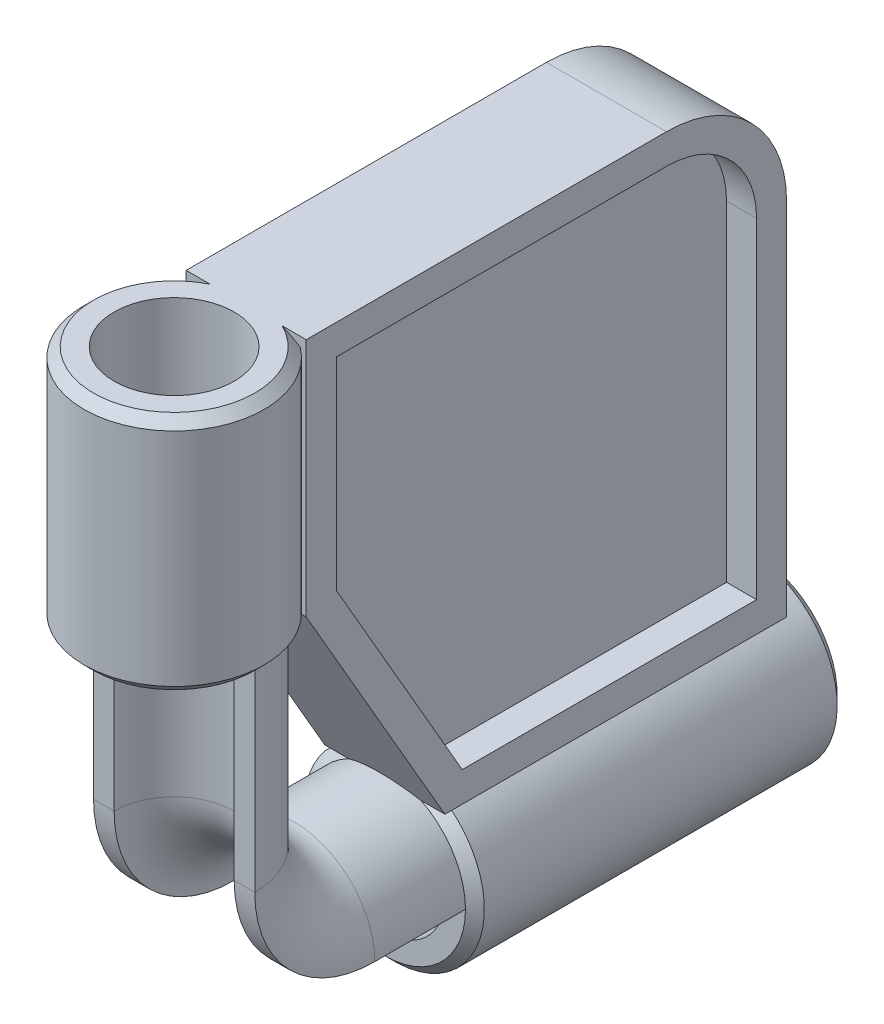
SolidWorks part; units mm, degrees
ref_plane "Front Plane" through (0, 0, 0) normal (1, 0, 0) x (0, 1, 0)
ref_plane "Top Plane" through (0, 0, 0) normal (0, 0, 1) x (0, 1, 0)
ref_plane "Right Plane" through (0, 0, 0) normal (0, 1, 0) x (-1, 0, 0)
sketch "Sketch1" plane through (0, 0, 0) normal (1, 0, 0) x (0, 1, 0)
  line L0 (-25.4, 10.7353) -> (0, 25.4)
  line L1 (-25.4, -25.4) -> (25.4, -25.4)
  line L2 (-25.4, -25.4) -> (-25.4, 10.7353)
  line L3 (0, 25.4) -> (25.4, 25.4)
  line L4 (25.4, -25.4) -> (25.4, 25.4)
  line L5 (0, -55) -> (0, 55) construction
  line L6 (55, 0) -> (-55, 0) construction
  point P0 (0, 0)
  point P10 (25.4, 0)
  dimension "D1" = 50.8
  dimension "D2" = 50.8
  dimension "D3" = 30
  dimension "D4" = 25.4
extrude "Boss-Extrude1" add sketch "Sketch1" along normal mid plane 12.7
fillet "Fillet1" radius 12.7 1 edges at (0, 25.4, -25.4)
sketch "Sketch3" plane through (6.35, 0, 0) normal (1, 0, 0) x (0, 1, 0)
  line L10 (-22.225, -22.225) -> (12.7, -22.225)
  line L11 (22.225, -12.7) -> (22.225, 22.225)
  line L12 (22.225, 22.225) -> (0.8507, 22.225)
  line L13 (0.8507, 22.225) -> (-22.225, 8.9022)
  line L14 (-22.225, 8.9022) -> (-22.225, -22.225)
  line L15 (-22.225, -22.225) -> (12.7, -22.225)
  line L16 (22.225, -12.7) -> (22.225, 22.225)
  line L17 (22.225, 22.225) -> (0.8507, 22.225)
  line L18 (0.8507, 22.225) -> (-22.225, 8.9022)
  line L19 (-22.225, 8.9022) -> (-22.225, -22.225)
  arc A2 (12.7, -22.225) -> (22.225, -12.7) centre (12.7, -12.7) ccw
  arc A3 (12.7, -22.225) -> (22.225, -12.7) centre (12.7, -12.7) ccw
  dimension "D1" = 3.175
extrude "Cut-Extrude2" cut sketch "Sketch3" against normal blind 3.175
mirror "Mirror1" about plane through (0, 0, 0) normal (1, 0, 0) of "Cut-Extrude2"
sketch "Sketch4" plane through (0, 0, -25.4) normal (0, 0, -1) x (1, 0, 0)
  line L0 (0, -27.94) -> (0, 27.94) construction
  line L1 (6.35, -25.4) -> (-6.35, -25.4) construction
  circle A0 centre (0, 33.02) radius 9.525
  circle A1 centre (0, 33.02) radius 6.35
  dimension "D1" = 19.05
  dimension "D2" = 12.7
  dimension "D3" = 58.42
extrude "Boss-Extrude2" add sketch "Sketch4" against normal up to vertex (36.1353 mm away) and the other way blind 3.175 up to point (6.35, -25.4, 10.7353)
sketch "Sketch5" plane through (0, 25.4, 0) normal (0, 1, 0) x (-1, 0, 0)
  line L0 (0, 29.6863) -> (0, -29.6863) construction
  line L1 (-5.715, -25.4) -> (5.715, -25.4) construction
  circle A0 centre (0, 33.02) radius 9.525
  circle A1 centre (0, 33.02) radius 6.35
  dimension "D1" = 19.05
  dimension "D2" = 12.7
  dimension "D3" = 58.42
extrude "Boss-Extrude3" add sketch "Sketch5" against normal up to surface (25.4 mm away) up to plane "Right Plane"
chamfer "Chamfer2" distance 1 angle 45 4 edges at (0, 0, 42.545) (0, -42.545, 10.7353) (0, -23.495, -28.575) (0, 25.4, 42.545)
sketch "Sketch6" plane through (0, 0, 0) normal (1, 0, 0) x (0, 1, 0)
  line L0 (-26.67, 10.7353) -> (-39.37, 10.7353) construction
  line L1 (-26.67, 10.7353) -> (-39.37, 10.7353) construction
  line L2 (0, 39.37) -> (0, 26.67) construction
  line L3 (0, 39.37) -> (0, 26.67) construction
  line L4 (-20.32, 33.02) -> (0, 33.02)
  line L5 (-33.02, 20.32) -> (-33.02, 10.7353)
  arc A0 (-33.02, 20.32) -> (-20.32, 33.02) centre (-20.32, 20.32) cw
  point P6 (-33.02, 10.7353)
  point P9 (0, 33.02)
  dimension "D1" = 12.7
sketch "Sketch7" plane through (0, 0, 0) normal (0, -1, 0) x (1, 0, 0)
  line L0 (-8.525, 33.02) -> (-6.35, 33.02)
  line L1 (6.35, 33.02) -> (8.525, 33.02)
  line L2 (0, 39.37) -> (0, 26.67) construction
  circle A0 centre (0, 33.02) radius 6.35 construction
  arc A4 (-6.35, 33.02) -> (6.35, 33.02) centre (0, 33.02) ccw
  arc A5 (-8.525, 33.02) -> (8.525, 33.02) centre (0, 33.02) ccw
  arc A6 (3.8225, 25.4) -> (-3.8225, 25.4) centre (0, 33.02) ccw construction
sweep "Sweep3" add profiles "Sketch7" path "Sketch6"
